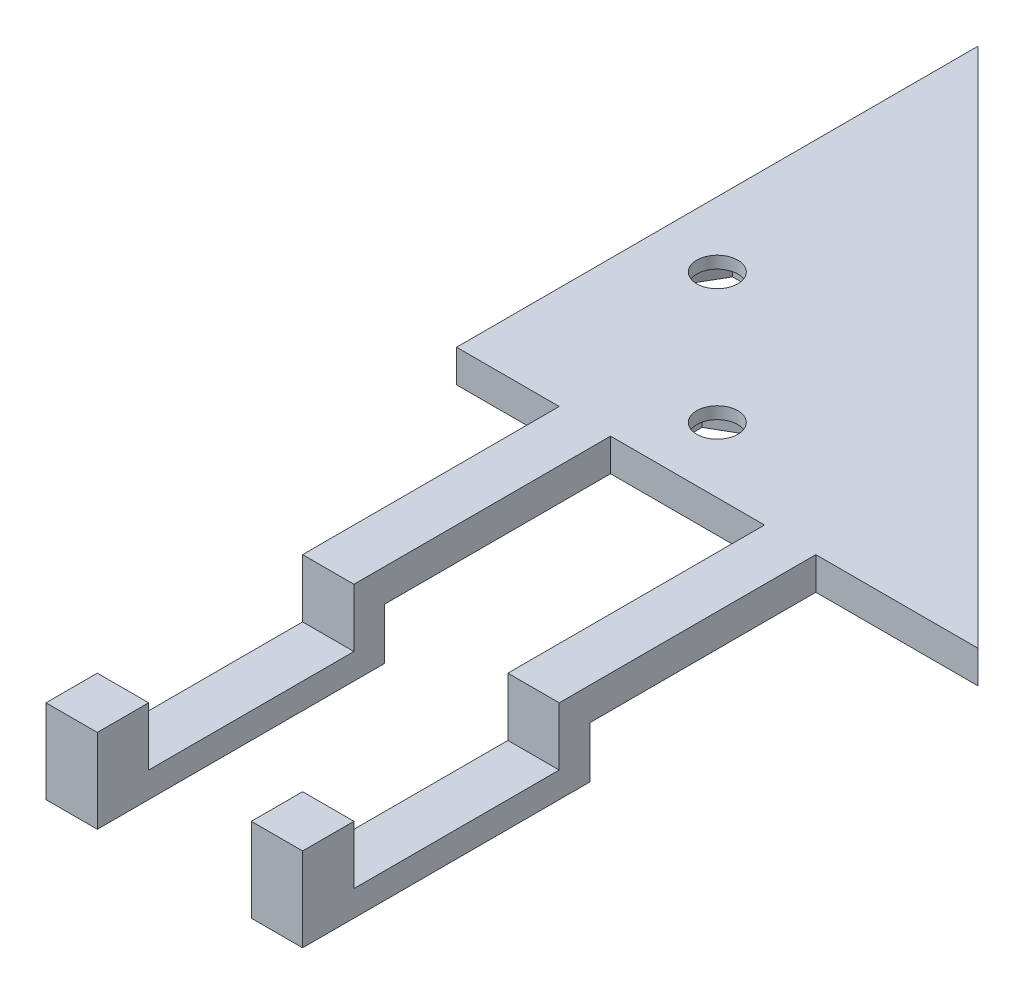
SolidWorks part; units mm, degrees
ref_plane "Front" through (0, 0, 0) normal (0, 0, 1) x (1, 0, 0)
ref_plane "Top" through (0, 0, 0) normal (0, 1, 0) x (1, 0, 0)
ref_plane "Right" through (0, 0, 0) normal (1, 0, 0) x (0, 0, -1)
sketch "Sketch1" plane through (0, 0, 0) normal (0, 1, 0) x (1, 0, 0)
  line L0 (0, 0) -> (50.8, 0)
  line L1 (-55, 0) -> (55, 0) construction
  line L2 (50.8, 0) -> (0, 50.8)
  line L3 (0, -55) -> (0, 55) construction
  line L4 (0, 50.8) -> (0, 0)
  dimension "D1" = 50.8
  dimension "D2" = 50.8
extrude "Boss-Extrude1" add sketch "Sketch1" along normal blind 3.175 contours L2 L4 L0
sketch "Sketch2" plane through (0, 3.175, 0) normal (0, 1, 0) x (1, 0, 0)
  line L0 (0, -55) -> (0, 55) construction
  line L1 (-55, 0) -> (55, 0) construction
  line L2 (0, 0) -> (25.4, 25.4) construction
  line L3 (50.8, 0) -> (0, 50.8) construction
  circle A0 centre (19.05, 6.35) radius 2
  circle A1 centre (6.35, 19.05) radius 2
  dimension "D1" = 4
  dimension "D3" = 6.35
  dimension "D2" = 19.05
extrude "Cut-Extrude1" cut sketch "Sketch2" against normal through all contours A0 | A1
sketch "Sketch3" plane through (0, 3.175, 0) normal (0, 1, 0) x (1, 0, 0)
  line L0 (0, 0) -> (25.4, 25.4) construction
  line L1 (8.3707, 15.55) -> (10.3914, 19.05)
  line L2 (10.3914, 19.05) -> (8.3707, 22.55)
  line L3 (0, 0) -> (50.8, 0)
  line L4 (50.8, 0) -> (0, 50.8)
  line L5 (0, 50.8) -> (0, 0)
  line L6 (0, 0) -> (50.8, 0)
  line L7 (50.8, 0) -> (0, 50.8)
  line L8 (0, 50.8) -> (0, 0)
  line L9 (8.3707, 22.55) -> (4.3293, 22.55)
  line L10 (4.3293, 22.55) -> (2.3086, 19.05)
  line L11 (2.3086, 19.05) -> (4.3293, 15.55)
  line L12 (4.3293, 15.55) -> (8.3707, 15.55)
  line L13 (22.55, 4.3293) -> (19.05, 2.3086)
  line L14 (19.05, 2.3086) -> (15.55, 4.3293)
  line L15 (15.55, 4.3293) -> (15.55, 8.3707)
  line L16 (15.55, 8.3707) -> (19.05, 10.3914)
  line L17 (19.05, 10.3914) -> (22.55, 8.3707)
  line L18 (22.55, 8.3707) -> (22.55, 4.3293)
  circle A0 centre (6.35, 19.05) radius 2 construction
  circle A1 centre (6.35, 19.05) radius 2
  circle A2 centre (19.05, 6.35) radius 2 construction
  circle A3 centre (19.05, 6.35) radius 2
  circle A4 centre (6.35, 19.05) radius 3.5 construction
  dimension "D2" = 7
  dimension "D1" = 0
extrude "Cut-Extrude2" cut sketch "Sketch3" along normal blind 2 from surface contours L2 L9 L10 L11 L12 L1 | L17 L18 L13 L14 L15 L16 starting at face at (6.35, 0, -21.05)
sketch "Sketch5" plane through (0, 0, 0) normal (1, 0, 0) x (0, 0, -1)
  line L0 (0, 4.4963) -> (0, -4.4963) construction
  line L1 (0, 3.175) -> (-25, 3.175)
  line L2 (0, 3.175) -> (0, 0)
  line L3 (0, 0) -> (-25, 0)
  line L4 (-25, 3.175) -> (-25, 0)
  line L5 (0, 3.175) -> (50.8, 3.175) construction
  line L6 (27.94, 0) -> (-27.94, 0) construction
  line L11 (-45, 0) -> (-50, 0)
  line L12 (-45, 0) -> (-45, 3.175)
  line L13 (-45, 3.175) -> (-50, 3.175)
  line L14 (-50, 0) -> (-50, 3.175)
  line L15 (-50, 0) -> (-22, 0)
  line L16 (-50, 0) -> (-50, -5)
  line L17 (-50, -5) -> (-22, -5)
  line L18 (-22, 0) -> (-22, -5)
  line L20 (-45, 0) -> (-25, 0)
  line L21 (-45, 0) -> (-45, -2.5)
  line L22 (-45, -2.5) -> (-25, -2.5)
  line L23 (-25, 0) -> (-25, -2.5)
  dimension "D1" = 3.175
  dimension "D2" = 25
  dimension "D3" = 5
  dimension "D4" = 25
  dimension "D5" = 3
  dimension "D6" = 5
  dimension "D7" = 2.5
extrude "Boss-Extrude2" add sketch "Sketch5" along normal blind 5 from offset 10 contours L14 L11 L12 L13 | L18 L3 L15 L11 L16 L17 | L1 L4 L3 L2 region at (0, 1.5875, 12.5) region at (0, -3.1944, 36.5556) region at (0, 1.5875, 47.5)
extrude "Boss-Extrude3" add sketch "Sketch5<3>" along normal blind 5 from offset 30 contours L18 L3 L15 L11 L16 L17 | L1 L4 L3 L2 | L13 L14 L11 L12 region at (0, 1.5875, 12.5) region at (0, -3.1944, 36.5556)
sketch "Sketch5<3>" plane through (0, 0, 0) normal (1, 0, 0) x (0, 0, -1) same geometry as "Sketch5"
